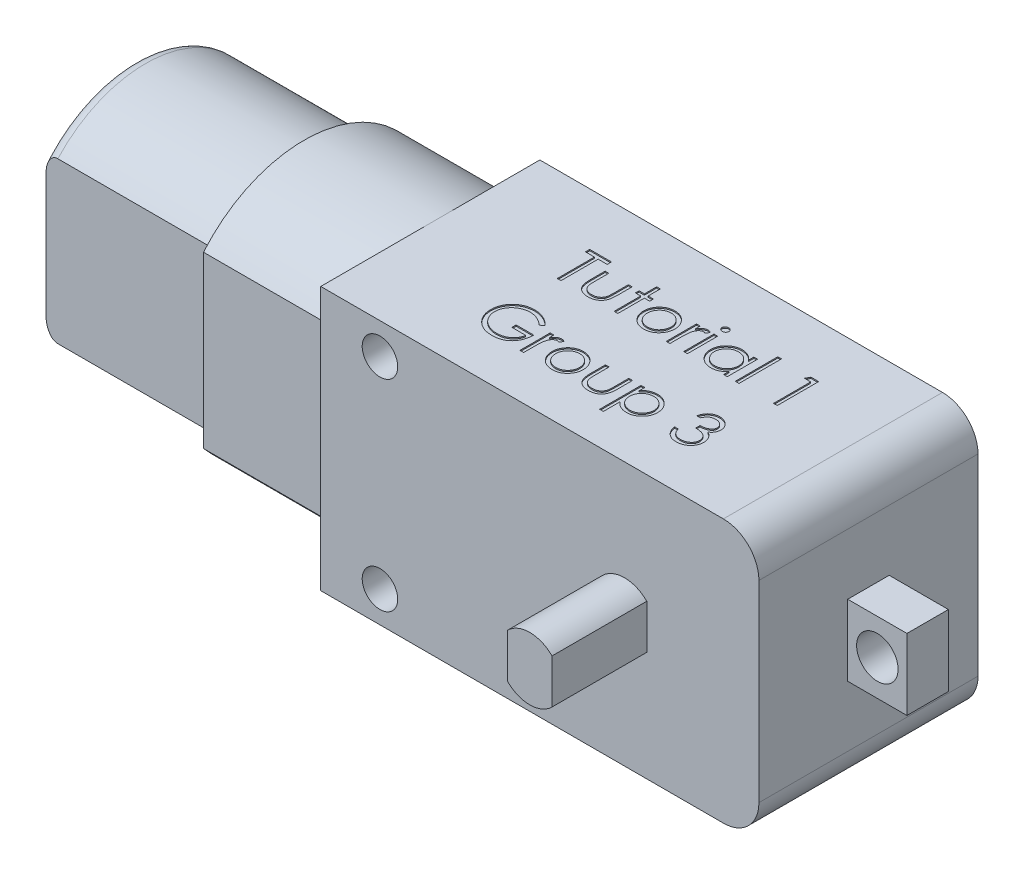
SolidWorks part; units mm, degrees
ref_plane "Front Plane" through (0, 0, 0) normal (0, 0, 1) x (1, 0, 0)
ref_plane "Top Plane" through (0, 0, 0) normal (0, 1, 0) x (1, 0, 0)
ref_plane "Right Plane" through (0, 0, 0) normal (1, 0, 0) x (0, 0, -1)
sketch "Sketch2" plane through (0, 0, 0) normal (0, 0, 1) x (1, 0, 0)
  line L0 (-18.5, 11.125) -> (18.5, -11.125) construction
  line L1 (-18.5, 11.125) -> (15.5, 11.125)
  line L2 (-18.5, 11.125) -> (-18.5, -11.125)
  line L3 (-18.5, -11.125) -> (15.5, -11.125)
  line L4 (18.5, 8.125) -> (18.5, -8.125)
  line L5 (-18.5, -11.125) -> (18.5, 11.125) construction
  arc A0 (15.5, -11.125) -> (18.5, -8.125) centre (15.5, -8.125) ccw
  arc A1 (15.5, 11.125) -> (18.5, 8.125) centre (15.5, 8.125) cw
  point P6 (18.5, -11.125)
  point P9 (18.5, 11.125)
  point P10 (0, 0)
  dimension "D3" = 3
  dimension "D1" = 37
  dimension "D2" = 22.25
extrude "Boss-Extrude3" add sketch "Sketch2" along normal blind 9.25 and the other way blind 9.25
sketch "Sketch7" plane through (-18.5, 0, 0) normal (-1, 0, 0) x (0, 0, 1)
  line L0 (-0.75, -11.125) -> (-0.75, 11.125) construction
  line L1 (7.75, -7.1774) -> (7.75, 7.1774)
  line L2 (-9.25, -7.1774) -> (-9.25, 7.1774)
  line L3 (9.25, 11.125) -> (9.25, -11.125) construction
  arc A0 (7.75, 7.1774) -> (-9.25, 7.1774) centre (-0.75, 0) ccw
  arc A1 (-9.25, -7.1774) -> (7.75, -7.1774) centre (-0.75, 0) ccw
  point P3 (-0.75, 0)
  point P10 (0, 0)
  point P12 (0, 0)
  dimension "D1" = 1.5
  dimension "D4" = 11.125
  dimension "D2" = 8.5
  dimension "D3" = 8.5
extrude "Boss-Extrude4" add sketch "Sketch7" along normal blind 11.4
sketch "Sketch8" plane through (-29.9, 0, 0) normal (-1, 0, 0) x (0, 0, 1)
  line L0 (6.65, -6.7632) -> (6.65, 6.7632)
  line L1 (-8.15, 6.7632) -> (-8.15, -6.7632)
  line L4 (-9.25, 7.1774) -> (-9.25, -7.1774) construction
  line L5 (7.75, -7.1774) -> (7.75, 7.1774) construction
  arc A0 (6.65, 6.7632) -> (-8.15, 6.7632) centre (-0.75, 0) ccw
  arc A1 (-8.15, -6.7632) -> (6.65, -6.7632) centre (-0.75, 0) ccw
  arc A2 (-0.75, -11.125) -> (7.75, -7.1774) centre (-0.75, 0) ccw construction
  arc A5 (-0.75, 11.125) -> (-9.25, 7.1774) centre (-0.75, 0) ccw construction
  point P10 (0, 0)
  point P11 (0, 0)
  point P14 (0, 0)
  dimension "D3" = 1.1
  dimension "D4" = 1.1
  dimension "D5" = 10.025
  dimension "D6" = 10.025
  dimension "D1" = 1.1
  dimension "D2" = 1.1
extrude "Boss-Extrude5" add sketch "Sketch8" along normal blind 8.8
sketch "Sketch9" plane through (-38.7, 0, 0) normal (-1, 0, 0) x (0, 0, 1)
  line L0 (-8.15, 6.7632) -> (-8.15, -6.7632)
  line L1 (6.65, 6.7632) -> (6.65, -6.7632)
  arc A0 (6.65, 6.7632) -> (-8.15, 6.7632) centre (-0.75, 0) ccw
  arc A1 (-8.15, -6.7632) -> (6.65, -6.7632) centre (-0.75, 0) ccw
  arc A2 (-8.15, -6.7632) -> (6.65, -6.7632) centre (-0.75, 0) ccw construction
extrude "Boss-Extrude6" add sketch "Sketch9" along normal blind 5.6
fillet "Fillet1" radius 1 2 edges at (-44.3, -10.025, -0.75) (-44.3, 10.025, -0.75)
sketch "Sketch10" plane through (-44.3, 0, 0) normal (-1, 0, 0) x (0, 0, 1)
  line L0 (2.65, 3.6661) -> (2.65, -3.6661)
  line L1 (6.65, -5.1663) -> (6.65, 5.1663) construction
  line L2 (-8.15, 6.7632) -> (-8.15, -6.7632) construction
  arc A0 (2.65, 3.6661) -> (2.65, -3.6661) centre (-0.75, 0) ccw
  point P3 (0, 0)
  point P8 (0, 0)
  dimension "D1" = 5
  dimension "D3" = 7.4
  dimension "D2" = 4
extrude "Boss-Extrude7" add sketch "Sketch10" along normal blind 1
sketch "Sketch11" plane through (-45.3, 0, 0) normal (-1, 0, 0) x (0, 0, 1)
  circle A0 centre (-0.75, 0) radius 1
  arc A1 (2.65, 3.6661) -> (2.65, -3.6661) centre (-0.75, 0) ccw construction
  dimension "D1" = 2
extrude "Boss-Extrude8" add sketch "Sketch11" along normal blind 1
sketch "Sketch12" plane through (0, 0, 9.25) normal (0, 0, 1) x (1, 0, 0)
  line L0 (0, 0) -> (-17.7021, 0) construction
  line L1 (-18.5, 11.125) -> (-18.5, -11.125) construction
  circle A0 centre (-13.5, 8.5) radius 1.5
  circle A1 centre (-13.5, -8.5) radius 1.5
  point P7 (0, 0)
  dimension "D1" = 3
  dimension "D2" = 17
  dimension "D3" = 5
extrude "Cut-Extrude1" cut sketch "Sketch12" against normal blind 30
sketch "Sketch13" plane through (0, 0, 9.25) normal (0, 0, 1) x (1, 0, 0)
  line L0 (18.5, -8.125) -> (18.5, 8.125) construction
  circle A0 centre (7.15, 0) radius 2.65
  point P2 (0, 0)
  point P3 (0, 0)
  point P7 (0, 0)
  point P8 (0, 0)
  dimension "D1" = 5.3
  dimension "D2" = 11.35
extrude "Boss-Extrude11" add sketch "Sketch13" along normal blind 8 and the other way blind 26.5
sketch "Sketch15" plane through (0, 0, 17.25) normal (0, 0, 1) x (1, 0, 0)
  line L0 (7.15, -2.65) -> (7.15, 2.65) construction
  line L1 (9.03, 1.8676) -> (9.8, 1.8676)
  line L2 (9.03, 1.8676) -> (9.03, -1.8676)
  line L3 (9.03, -1.8676) -> (9.8, -1.8676)
  line L4 (9.8, 1.8676) -> (9.8, -1.8676)
  line L5 (5.27, -1.8676) -> (4.5, -1.8676)
  line L6 (5.27, -1.8676) -> (5.27, 1.8676)
  line L7 (5.27, 1.8676) -> (4.5, 1.8676)
  line L8 (4.5, -1.8676) -> (4.5, 1.8676)
  circle A0 centre (7.15, 0) radius 2.65 construction
  point P13 (9.03, -1.8676)
  point P14 (5.27, -1.8676)
  point P15 (5.27, 1.8676)
  dimension "D1" = 3.76
extrude "Cut-Extrude3" cut sketch "Sketch15" against normal blind 8
sketch "Sketch16" plane through (0, 0, -17.25) normal (0, 0, -1) x (-1, 0, 0)
  line L0 (-7.15, -2.65) -> (-7.15, 2.65) construction
  line L1 (-5.27, 1.8676) -> (-4.5, 1.8676)
  line L2 (-5.27, 1.8676) -> (-5.27, -1.8676)
  line L3 (-5.27, -1.8676) -> (-4.5, -1.8676)
  line L4 (-4.5, 1.8676) -> (-4.5, -1.8676)
  line L5 (-9.03, -1.8676) -> (-9.8, -1.8676)
  line L6 (-9.03, -1.8676) -> (-9.03, 1.8676)
  line L7 (-9.03, 1.8676) -> (-9.8, 1.8676)
  line L8 (-9.8, -1.8676) -> (-9.8, 1.8676)
  circle A0 centre (-7.15, 0) radius 2.65 construction
  circle A1 centre (-7.15, 0) radius 2.65 construction
  point P15 (-9.03, -1.8676)
  point P16 (-9.03, 1.8676)
  point P17 (-5.27, 1.8676)
  point P18 (-5.27, -1.8676)
  dimension "D1" = 3.76
extrude "Cut-Extrude4" cut sketch "Sketch16" against normal blind 8
sketch "Sketch17" plane through (18.5, 0, 0) normal (1, 0, 0) x (0, 0, -1)
  line L0 (-1.75, -3) -> (1.75, 3) construction
  line L1 (-1.75, 3) -> (1.75, 3)
  line L2 (-1.75, 3) -> (-1.75, -3)
  line L3 (-1.75, -3) -> (1.75, -3)
  line L4 (1.75, 3) -> (1.75, -3)
  line L5 (-1.75, 3) -> (1.75, -3) construction
  point P4 (0, 0)
  dimension "D1" = 6
  dimension "D2" = 3.5
extrude "Boss-Extrude12" add sketch "Sketch17" along normal blind 5
sketch "Sketch18" plane through (0, 0, 1.75) normal (0, 0, 1) x (1, 0, 0)
  line L0 (18.5, 3) -> (23.5, -3) construction
  line L1 (18.5, -3) -> (23.5, 3) construction
  circle A0 centre (21, 0) radius 1.75
  dimension "D1" = 3.5
extrude "Cut-Extrude5" cut sketch "Sketch18" against normal blind 5
sketch "Sketch19" plane through (0, 11.125, 0) normal (0, 1, 0) x (1, 0, 0)
  text T0 "Tutorial 1\r\nGroup 3"
extrude "Cut-Extrude6" cut sketch "Sketch19" against normal blind 0.1
